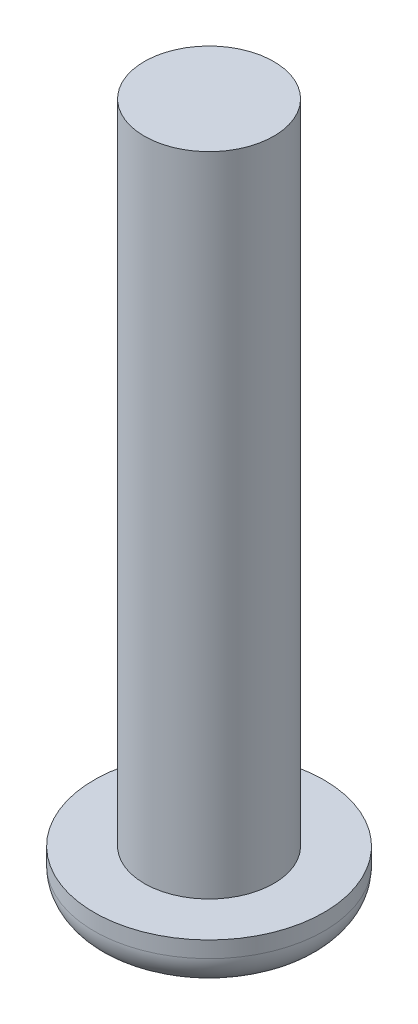
SolidWorks part; units mm, degrees
ref_plane "Front Plane" through (0, 0, 0) normal (0, 0, 1) x (1, 0, 0)
ref_plane "Top Plane" through (0, 0, 0) normal (0, 1, 0) x (1, 0, 0)
ref_plane "Right Plane" through (0, 0, 0) normal (1, 0, 0) x (0, 0, -1)
sketch "Sketch1" plane through (0, 0, 0) normal (0, 1, 0) x (1, 0, 0)
  circle A0 centre (0, 0) radius 4
  dimension "D1" = 8
extrude "Boss-Extrude1" add sketch "Sketch1" along normal blind 40 contours A0
sketch "Sketch2" plane through (0, 0, 0) normal (0, -1, 0) x (1, 0, 0)
  circle A0 centre (0, 0) radius 7.1
  circle A1 centre (0, 0) radius 4 construction
  circle A2 centre (0, 0) radius 4 construction
  dimension "D1" = 14.2
extrude "Boss-Extrude2" add sketch "Sketch2" along normal blind 3
fillet "Fillet1" radius 2 1 edges at (0, -3, -7.1)
sketch "Sketch3" plane through (0, -3, 0) normal (0, -1, 0) x (1, 0, 0)
  line L0 (0.375, 0.375) -> (1.5, 0.375)
  line L1 (-0.375, -1.5) -> (0.375, -1.5)
  line L2 (-0.375, -1.5) -> (-0.375, -0.375)
  line L3 (-0.375, 1.5) -> (0.375, 1.5)
  line L4 (0.375, -1.5) -> (0.375, -0.375)
  line L7 (-1.5, -0.375) -> (-0.375, -0.375)
  line L8 (-1.5, -0.375) -> (-1.5, 0.375)
  line L9 (-1.5, 0.375) -> (-0.375, 0.375)
  line L10 (1.5, -0.375) -> (1.5, 0.375)
  line L15 (0.375, 0.375) -> (0.375, 1.5)
  line L16 (0.375, -0.375) -> (1.5, -0.375)
  line L17 (-0.375, 0.375) -> (-0.375, 1.5)
  point P0 (0, 0)
  point P6 (0, 0)
  dimension "D1" = 3
  dimension "D2" = 0.75
extrude "Cut-Extrude1" cut sketch "Sketch3" against normal blind 1 draft 15
sketch "Sketch5" [suppressed] plane through (0, 0, 0) normal (0, 0, 1) x (1, 0, 0)
  line L0 (-2.1, -2) -> (2.1, -2) construction
  line L3 (0, 0) -> (0, 24) construction
  point P6 (0, 11)
  dimension "D1" = 13
  dimension "D2" = 26
sketch "Sketch6" plane through (0, 0, 0) normal (0, 0, 1) x (1, 0, 0)
  line L0 (0, 0) -> (0, 40) construction
  line L1 (4, 40) -> (-4, 40) construction
